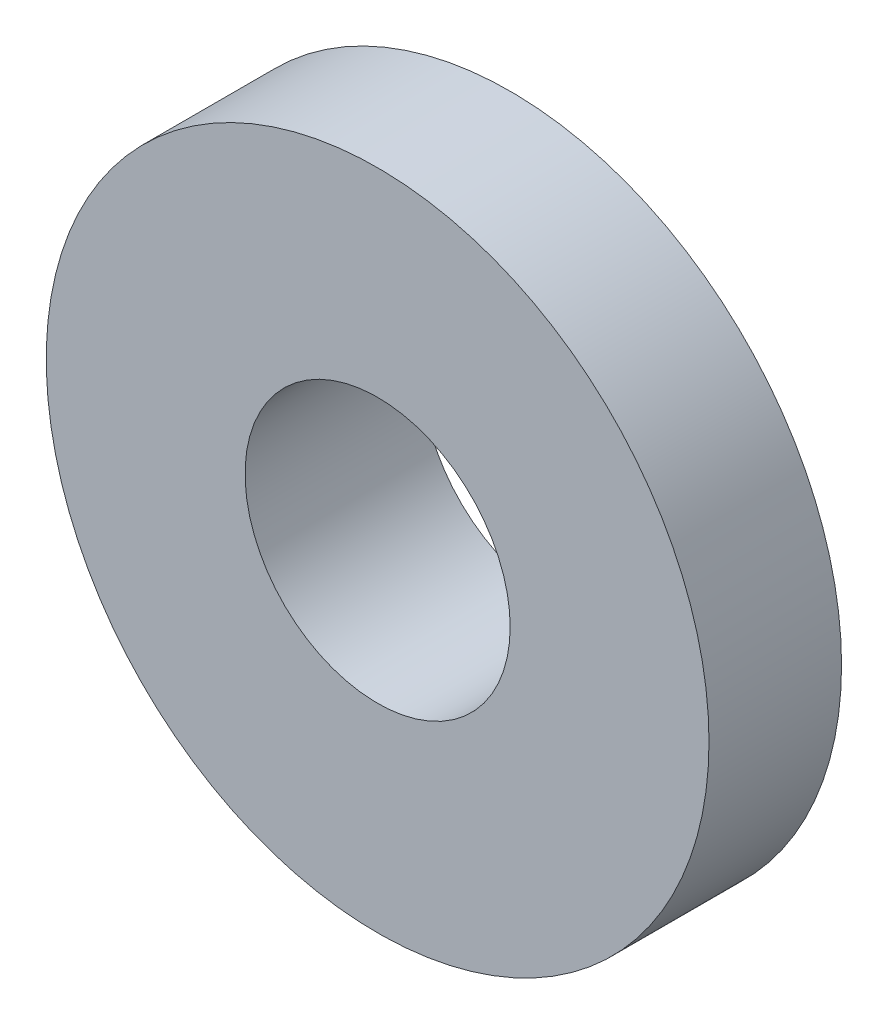
SolidWorks part; units mm, degrees
ref_plane "Plan de face" through (0, 0, 0) normal (0, 0, 1) x (1, 0, 0)
ref_plane "Plan de dessus" through (0, 0, 0) normal (0, 1, 0) x (1, 0, 0)
ref_plane "Plan de droite" through (0, 0, 0) normal (1, 0, 0) x (0, 0, -1)
sketch "Esquisse1" plane through (0, 0, 0) normal (0, 0, 1) x (1, 0, 0)
  circle A0 centre (0, 0) radius 1.5
  circle A1 centre (0, 0) radius 2.5
  circle A2 centre (0, 0) radius 3.75
  dimension "D1" = 3
  dimension "D2" = 5
  dimension "D3" = 7.5
extrude "Boss.-Extru.1" add sketch "Esquisse1" along normal blind 1.5 contours A2 A1 | A1 A0 region at (-2.4293, 0, 0) region at (-3.6439, 0, 0)
extrude "Boss.-Extru.2" add sketch "Esquisse1<3>" against normal blind 0.5 contours A1 A0 region at (-2.4293, 0, 0)
sketch "Esquisse1<3>" plane through (0, 0, 0) normal (0, 0, 1) x (1, 0, 0) same geometry as "Esquisse1"
